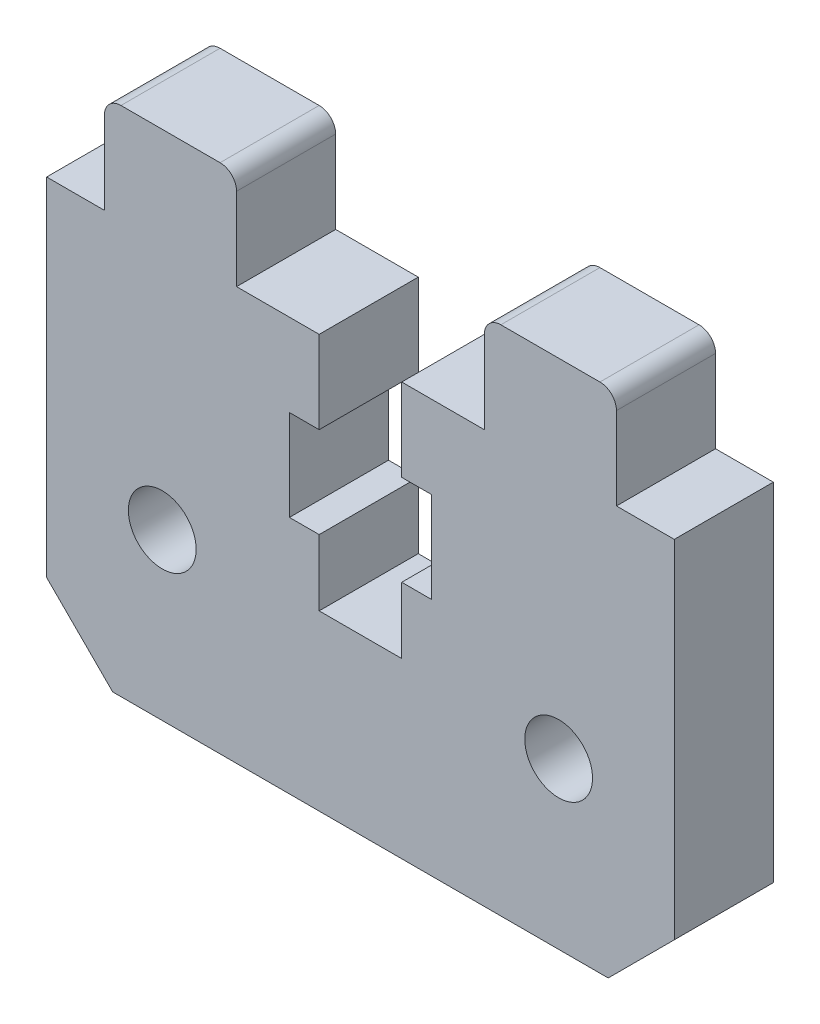
SolidWorks part; units mm, degrees
ref_plane "Plan de face" through (0, 0, 0) normal (0, 0, 1) x (1, 0, 0)
ref_plane "Plan de dessus" through (0, 0, 0) normal (0, 1, 0) x (1, 0, 0)
ref_plane "Plan de droite" through (0, 0, 0) normal (1, 0, 0) x (0, 0, -1)
sketch "Esquisse1" plane through (0, 0, 0) normal (0, 0, 1) x (1, 0, 0)
  line L1 (-19, 12.5) -> (19, 12.5)
  line L2 (-19, 12.5) -> (-19, -12.5)
  line L3 (-19, -12.5) -> (19, -12.5)
  line L4 (19, 12.5) -> (19, -12.5)
  line L5 (-19, 12.5) -> (19, -12.5) construction
  line L6 (-19, -12.5) -> (19, 12.5) construction
  point P0 (0, 0)
  dimension "D1" = 38
  dimension "D2" = 25
extrude "Boss.-Extru.1" add sketch "Esquisse1" along normal blind 6
sketch "Esquisse2" plane through (0, 0, 6) normal (0, 0, 1) x (1, 0, 0)
  line L0 (19, 12.5) -> (-19, 12.5) construction
  line B0 (-15.5, 12.5) -> (-15.5, 17.5)
  line B1 (-14.5, 18.5) -> (-8.5, 18.5)
  line B2 (-7.5, 17.5) -> (-7.5, 12.5)
  line B3 (-7.5, 12.5) -> (-2.5, 12.5)
  line B4 (-2.5, 12.5) -> (-2.5, 7.5)
  line B5 (-2.5, 7.5) -> (-4.3, 7.5)
  line B6 (-4.3, 7.5) -> (-4.3, 2)
  line B7 (-4.3, 2) -> (-2.5, 2)
  line B8 (-2.5, 2) -> (-2.5, -2)
  line B9 (-2.5, -2) -> (2.5, -2)
  line B10 (0, -2) -> (0, 12.5) construction
  line B11 (15.5, 12.5) -> (7.5, 12.5)
  line B12 (-7.5, 12.5) -> (-15.5, 12.5)
  line B13 (2.5, 2) -> (2.5, -2)
  line B14 (4.3, 2) -> (2.5, 2)
  line B15 (4.3, 7.5) -> (4.3, 2)
  line B16 (2.5, 7.5) -> (4.3, 7.5)
  line B17 (2.5, 12.5) -> (2.5, 7.5)
  line B18 (7.5, 12.5) -> (2.5, 12.5)
  line B19 (7.5, 17.5) -> (7.5, 12.5)
  line B20 (14.5, 18.5) -> (8.5, 18.5)
  line B21 (15.5, 12.5) -> (15.5, 17.5)
  line B22 (-2.5, 12.5) -> (2.5, 12.5)
  arc B23 (-8.5, 18.5) -> (-7.5, 17.5) centre (-8.5, 17.5) cw
  arc B24 (-15.5, 17.5) -> (-14.5, 18.5) centre (-14.5, 17.5) cw
  arc B25 (15.5, 17.5) -> (14.5, 18.5) centre (14.5, 17.5) ccw
  arc B26 (8.5, 18.5) -> (7.5, 17.5) centre (8.5, 17.5) ccw
  line M2 (19, 12.5) -> (-19, 12.5)
sketch_block_instance "attache_male-1"
sketch_block "attache_male" parameters "D7"=1, "D1"=5, "D2"=5, "D3"=5.5, "D4"=1.8, "D5"=4, "D6"=2.5
extrude "Enlèv. mat.-Extru.1" cut sketch "Esquisse2" against normal blind 6 contours B17 B4 B5 B6 B7 B8 B9 B13 B14 B15 B16 M2 region at (0, 5.1427, 6)
extrude "Boss.-Extru.2" add sketch "Esquisse2<3>" against normal blind 6 contours B24 B0 B2 B23 B1 M2 | B20 B26 B19 B21 B25 M2 region at (11.5, 15.4749, 6) region at (-11.5, 15.4749, 6)
sketch "Esquisse2<3>" plane through (0, 0, 6) normal (0, 0, 1) x (1, 0, 0) same geometry as "Esquisse2"
sketch "Esquisse4" plane through (0, 0, 6) normal (0, 0, 1) x (1, 0, 0)
  line L0 (-19, -12.5) -> (19, -12.5) construction
  line L1 (-19, 12.5) -> (-19, -12.5) construction
  circle A0 centre (-12, -2.5) radius 2.0524
  dimension "D3" = 4.1048
  dimension "D1" = 10
  dimension "D2" = 7
extrude "Enlèv. mat.-Extru.2" cut sketch "Esquisse4" against normal blind 6
mirror "Symétrie7" about plane through (0, 0, 0) normal (1, 0, 0) of "Enlèv. mat.-Extru.2"
chamfer "Chanfrein2" distance 4 angle 45 2 edges at (-19, -12.5, 3) (19, -12.5, 3)
